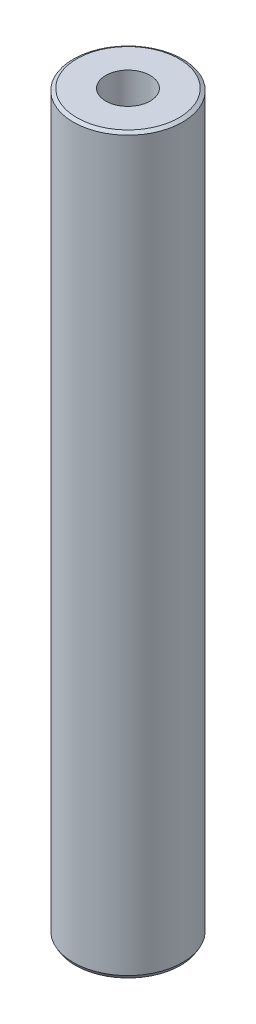
SolidWorks part; units mm, degrees
ref_plane "Front Plane" through (0, 0, 0) normal (0, 0, 1) x (1, 0, 0)
ref_plane "Top Plane" through (0, 0, 0) normal (0, 1, 0) x (1, 0, 0)
ref_plane "Right Plane" through (0, 0, 0) normal (1, 0, 0) x (0, 0, -1)
sketch "Sketch1" plane through (0, 0, 0) normal (0, 1, 0) x (1, 0, 0)
  circle A0 centre (0, 0) radius 32.5
  dimension "SHAFT_OD" = 65
extrude "Boss-Extrude1" add sketch "Sketch1" along normal blind 436.2541
sketch "Sketch2" plane through (0, 0, 0) normal (0, 1, 0) x (1, 0, 0)
  circle A0 centre (0, 0) radius 13.2352
  dimension "BORE_D" = 26.4705
extrude "Cut-Extrude1" cut sketch "Sketch2" along normal through all
chamfer "Chamfer1" distance 1.217 angle 60 2 edges at (0, 436.2541, 32.5) (0, 0, 32.5) first distance on face at (0, 436.2541, 32.5) first distance on face at (0, 0, 13.2352)
